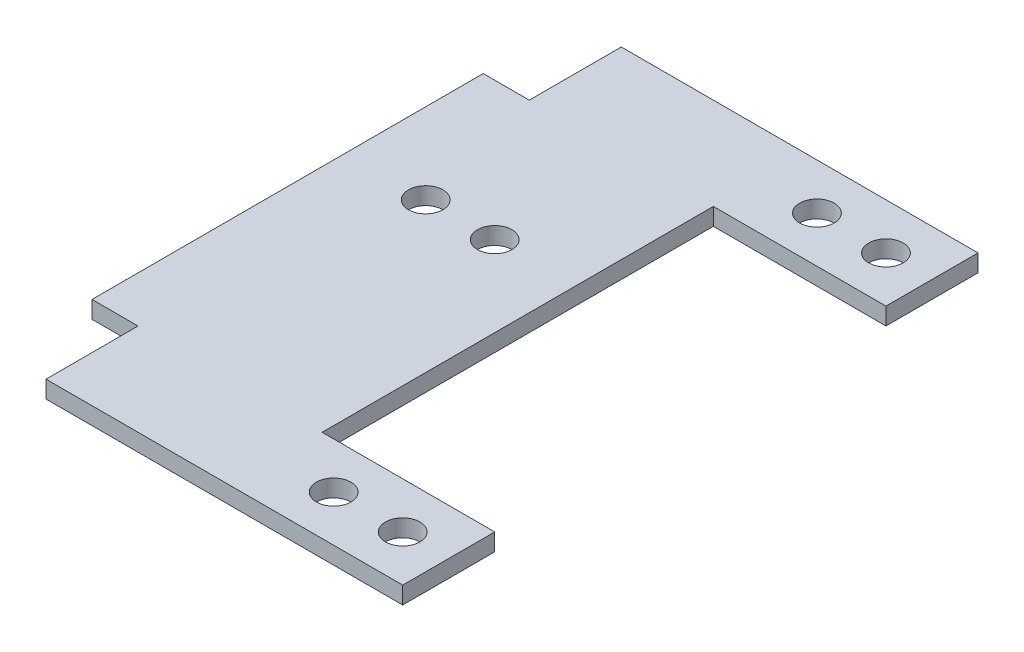
SolidWorks part; units mm, degrees
note: The reader was unsure of these and kept them because the rebuilt part matched: thickness of "Base-Flange1", "Tab1", "Sheet-Metal1", "Sheet-Metal2", "Sheet-Metal3", "Sheet-Metal7".
material "1060 Alloy"
ref_plane "Front Plane" through (0, 0, 0) normal (0, 0, 1) x (1, 0, 0)
ref_plane "Top Plane" through (0, 0, 0) normal (0, 1, 0) x (1, 0, 0)
ref_plane "Right Plane" through (0, 0, 0) normal (1, 0, 0) x (0, 0, -1)
sketch "Sketch1" plane through (0, 0, 0) normal (0, 1, 0) x (1, 0, 0)
  line L1 (-10, 17) -> (10, 17)
  line L2 (-10, 17) -> (-10, -17)
  line L3 (-10, -17) -> (10, -17)
  line L4 (10, 17) -> (10, -17)
  line L5 (-10, 17) -> (10, -17) construction
  line L6 (-10, -17) -> (10, 17) construction
  point P0 (0, 0)
  dimension "D1" = 34
  dimension "D2" = 20
base flange "Base-Flange1" sketch "Sketch1" thickness 1.5 reverse thickness direction yes parameters "D1"=0.7366
sketch "Sketch2" plane through (0, 1.5, 0) normal (0, 1, 0) x (1, 0, 0)
  line L0 (-6, -17) -> (-6, -25)
  line L1 (-10, -17) -> (10, -17) construction
  line L2 (-6, -25) -> (25, -25)
  line L3 (25, -25) -> (25, -17)
  line L4 (-6, -17) -> (25, -17)
  line L5 (-14.1953, 0) -> (17.2773, 0) construction
  line L6 (25, 25) -> (25, 17)
  line L7 (-6, 17) -> (25, 17)
  line L8 (-6, 17) -> (-6, 25)
  line L9 (-6, 25) -> (25, 25)
  dimension "D1" = 8
  dimension "D2" = 31
  dimension "D3" = 6
base flange "Tab1" sketch "Sketch2" thickness 1.5 reverse thickness direction no parameters "D1"=0.7366
sketch "Sketch4" plane through (0, 1.5, 0) normal (0, 1, 0) x (1, 0, 0)
  line L0 (-3, 5) -> (3, 5) construction
  circle A2 centre (-3, 5) radius 1.5
  circle A3 centre (3, 5) radius 1.5
  point P4 (0, 5)
  dimension "D1" = 3
  dimension "D2" = 6
  dimension "D3" = 12
extrude "Cut-Extrude1" cut sketch "Sketch4" against normal blind 10 normal cut yes
sketch "Sketch5" plane through (0, 1.5, 0) normal (0, 1, 0) x (1, 0, 0)
  line L0 (15, 21) -> (21, 21) construction
  line L1 (21, 21) -> (21, -21) construction
  line L2 (21, -21) -> (15, -21) construction
  line L3 (15, -21) -> (15, 21) construction
  line L4 (25, 25) -> (-6, 25) construction
  line L5 (25, -25) -> (25, -17) construction
  circle A0 centre (21, 21) radius 1.5
  circle A1 centre (15, 21) radius 1.5
  circle A2 centre (15, -21) radius 1.5
  circle A3 centre (21, -21) radius 1.5
  point P10 (0, 0)
  point P13 (18, -21)
  dimension "D2" = 3
  dimension "D1" = 6
  dimension "D3" = 42
  dimension "D4" = 4
  dimension "D5" = 7
extrude "Cut-Extrude2" cut sketch "Sketch5" against normal blind 10 normal cut yes
sketch "Bend-Lines1" [suppressed] plane through (0, 0, 0) normal (0, 1, 0) x (1, 0, 0)
sketch "Bounding-Box1" [suppressed] plane through (0, 0, 0) normal (0, 1, 0) x (1, 0, 0)
sheet metal parameters "Sheet-Metal1" thickness 1.5 parameters "D1"=0.7366
flat pattern "Flat-Pattern1" [suppressed]
sketch "Bend-Lines2" plane through (0, 0, 0) normal (0, 1, 0) x (1, 0, 0)
sketch3d "Bounding-Box2" [suppressed]
  line L0 (10, 17, 0) -> (10, -17, 0) construction
  line L1 (-10, 17, 0) -> (-10, -17, 0) construction
  line L2 (10, 17, 0) -> (-10, 17, 0) construction
  line L3 (10, -17, 0) -> (-10, -17, 0) construction
sheet metal parameters "Sheet-Metal2" thickness 1.5 parameters "D1"=0.7366
flat pattern "Flat-Pattern2"
sketch "Bend-Lines3" plane through (0, 0, 0) normal (0, -1, 0) x (-1, 0, 0)
  point P0 (-6, -17.36)
  point P1 (6, -17.36)
  point P2 (6, 17.36)
  point P3 (-6, 17.36)
sketch3d "Bounding-Box3" [suppressed]
  line L0 (10, 23, 0) -> (10, -23, 0) construction
  line L1 (-10, 23, 0) -> (-10, -23, 0) construction
  line L2 (10, 23, 0) -> (-10, 23, 0) construction
  line L3 (10, -23, 0) -> (-10, -23, 0) construction
sheet metal parameters "Sheet-Metal3" thickness 1.5 parameters "D1"=0.7366
flat pattern "Flat-Pattern2"
sketch "Bend-Lines3" plane through (0, 0, 0) normal (0, -1, 0) x (-1, 0, 0)
sketch3d "Bounding-Box3" [suppressed]
  line L0 (10, 25, 0) -> (10, -25, 0) construction
  line L1 (-24, 25, 0) -> (-24, -25, 0) construction
  line L2 (10, 25, 0) -> (-24, 25, 0) construction
  line L3 (10, -25, 0) -> (-24, -25, 0) construction
sheet metal parameters "Sheet-Metal7" thickness 1.5 parameters "D1"=0.7366
flat pattern "Flat-Pattern2"
sketch "Bend-Lines3" plane through (0, 0, 0) normal (0, -1, 0) x (-1, 0, 0)
sketch3d "Bounding-Box3" [suppressed]
  line L0 (10, 25, 0) -> (10, -25, 0) construction
  line L1 (-25, 25, 0) -> (-25, -25, 0) construction
  line L2 (10, 25, 0) -> (-25, 25, 0) construction
  line L3 (10, -25, 0) -> (-25, -25, 0) construction
